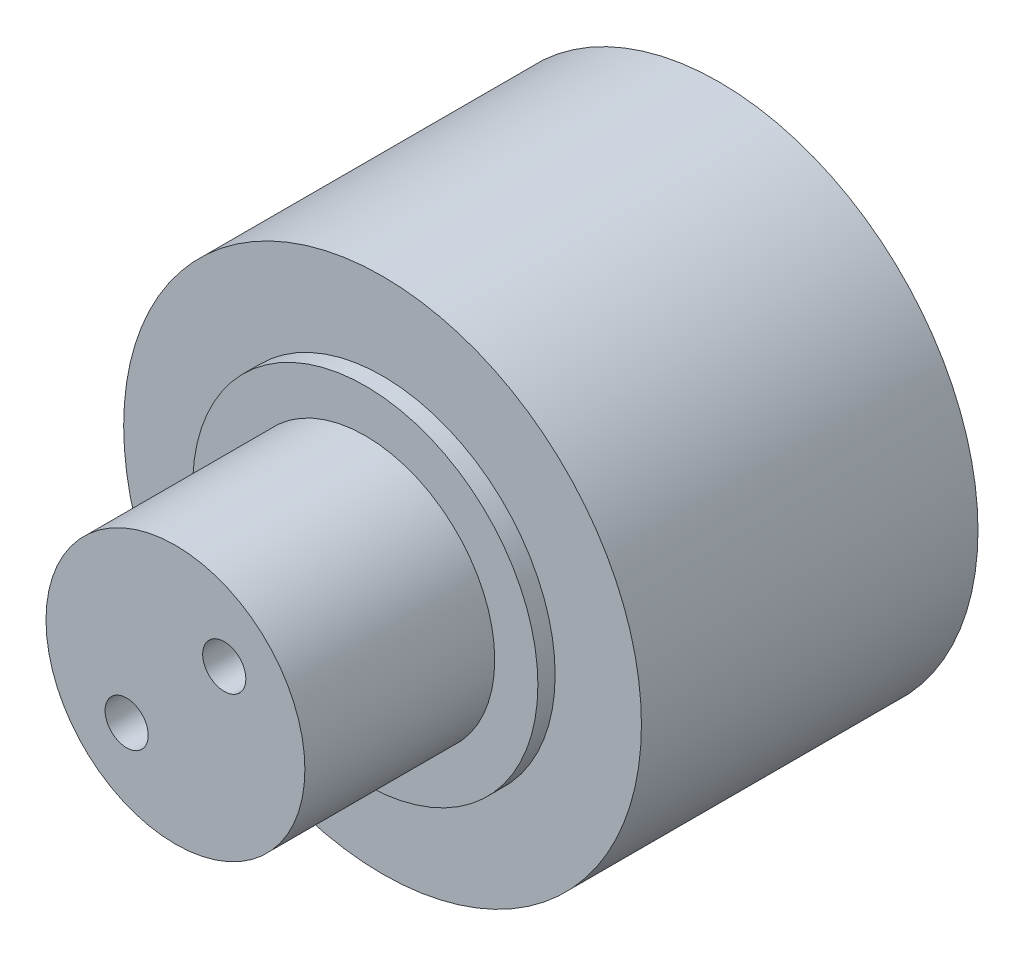
SolidWorks part; units mm, degrees
ref_plane "Спереди" through (0, 0, 0) normal (0, 0, 1) x (1, 0, 0)
ref_plane "Сверху" through (0, 0, 0) normal (0, 1, 0) x (1, 0, 0)
ref_plane "Справа" through (0, 0, 0) normal (1, 0, 0) x (0, 0, -1)
sketch "Эскиз1" plane through (0, 0, 0) normal (0, 0, 1) x (1, 0, 0)
  circle A0 centre (0, 0) radius 15
  dimension "D1" = 30
extrude "Бобышка-Вытянуть1" add sketch "Эскиз1" along normal blind 19.5
sketch "Эскиз2" plane through (0, 0, 19.5) normal (0, 0, 1) x (1, 0, 0)
  circle A0 centre (0, 0) radius 10
  dimension "D1" = 20
extrude "Бобышка-Вытянуть2" add sketch "Эскиз2" along normal blind 1
sketch "Эскиз3" plane through (0, 0, 20.5) normal (0, 0, 1) x (1, 0, 0)
  circle A0 centre (0, 0) radius 7.5
  dimension "D1" = 15
extrude "Бобышка-Вытянуть3" add sketch "Эскиз3" along normal blind 11
sketch "Эскиз4" plane through (0, 0, 0) normal (0, 0, -1) x (-1, 0, 0)
  line L0 (0, 15) -> (0, -15) construction
  line L1 (-15, 0) -> (15, 0) construction
  circle A0 centre (0, 0) radius 15 construction
  circle A1 centre (0, 0) radius 10 construction
  dimension "D1" = 20
hole_wizard "Отверстие обработанное метчиком M3x0.52" positions "Эскиз6" profile "Эскиз5" tap size "M3x0.5" standard "Ansi Metric"
sketch "Эскиз6" plane through (0, 0, 0) normal (0, 0, -1) x (-1, 0, 0)
  line L0 (0, 15) -> (0, -15) construction
  line L1 (-15, 0) -> (15, 0) construction
  circle A0 centre (0, 0) radius 10 construction
  point P0 (0, 10)
  point P6 (10, 0)
  point P10 (-10, 0)
  point P12 (0, -10)
cosmetic thread "Отверстие резьбы1" parameters "D2"=3
cosmetic thread "Отверстие резьбы2" parameters "D2"=3
cosmetic thread "Отверстие резьбы3" parameters "D2"=3
cosmetic thread "Отверстие резьбы4" parameters "D2"=3
sketch "Эскиз5" plane through (0, 10, 0) normal (1, 0, 0) x (0, 1, 0)
  line L0 (0, 0) -> (0, 13.2511)
  line L1 (0, 13.2511) -> (1.25, 12.5)
  line L2 (1.25, 12.5) -> (1.25, 0)
  line L5 (1.25, 0) -> (0, 0)
  line L10 (0, 13.2511) -> (-1.25, 12.5) construction
  line L11 (0, -6.35) -> (0, 107.95) construction
  dimension "Диаметр сверла" = 2.5
  dimension "Глубина сверла" = 12.5
  dimension "Угол заточки сверла" = 118
sketch "Эскиз7" plane through (0, 0, 31.5) normal (0, 0, 1) x (1, 0, 0)
  line L0 (2.8284, 2.8284) -> (-2.8284, -2.8284) construction
  line L1 (15, 0) -> (-15, 0) construction
  line L2 (-2.8284, 2.8284) -> (2.8284, -2.8284) construction
  circle A0 centre (0, 0) radius 4 construction
  dimension "D1" = 8
  dimension "D2" = 45
hole_wizard "Отверстие обработанное метчиком M3x0.51" positions "Эскиз9" profile "Эскиз8" tap size "M3x0.5" standard "Ansi Metric"
sketch "Эскиз9" plane through (0, 0, 31.5) normal (0, 0, 1) x (1, 0, 0)
  point P0 (-2.8284, -2.8284)
  point P3 (2.8284, 2.8284)
cosmetic thread "Отверстие резьбы5" parameters "D1"=8, "D2"=3
cosmetic thread "Отверстие резьбы6" parameters "D1"=8, "D2"=3
sketch "Эскиз8" plane through (-2.8284, -2.8284, 31.5) normal (1, 0, 0) x (0, -1, 0)
  line L0 (0, 0) -> (0, 8.7511)
  line L1 (0, 8.7511) -> (1.25, 8)
  line L2 (1.25, 8) -> (1.25, 0)
  line L5 (1.25, 0) -> (0, 0)
  line L10 (0, 8.7511) -> (-1.25, 8) construction
  line L11 (0, -6.35) -> (0, 107.95) construction
  dimension "Диаметр сверла" = 2.5
  dimension "Глубина сверла" = 8
  dimension "Угол заточки сверла" = 118
sketch "Эскиз10" plane through (0, 0, 0) normal (0, 0, -1) x (-1, 0, 0)
  line L0 (-15, 15) -> (15, 15) construction
  line L1 (15, 15) -> (15, 10.644) construction
  line L2 (-15, 15) -> (-15, 10.1251) construction
  circle A0 centre (0, 0) radius 15 construction
